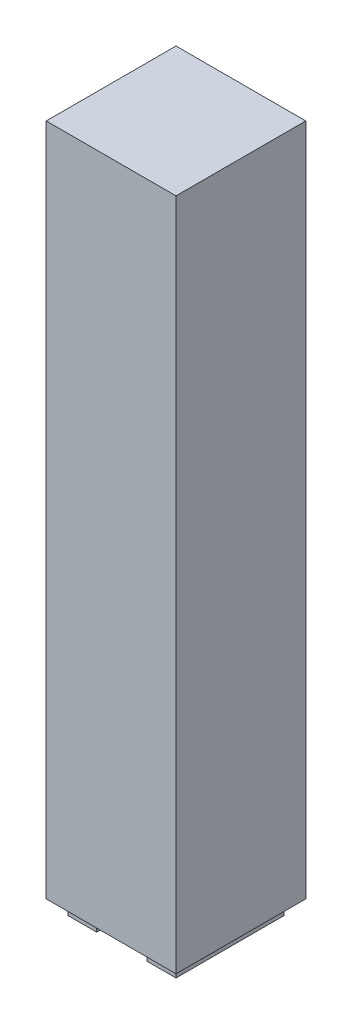
SolidWorks part; units mm, degrees
ref_plane "Front Plane" through (0, 0, 0) normal (0, 0, 1) x (1, 0, 0)
ref_plane "Top Plane" through (0, 0, 0) normal (0, 1, 0) x (1, 0, 0)
ref_plane "Right Plane" through (0, 0, 0) normal (1, 0, 0) x (0, 0, -1)
sketch "Sketch1" plane through (0, 0, 0) normal (0, 1, 0) x (1, 0, 0)
  line L1 (0, 0) -> (36, 0)
  line L2 (0, 0) -> (0, 36)
  line L3 (0, 36) -> (36, 36)
  line L4 (36, 0) -> (36, 36)
  dimension "D1" = 36
  dimension "D2" = 36
extrude "Boss-Extrude1" add sketch "Sketch1" along normal blind 186.9
sketch "Sketch2" plane through (0, 0, 0) normal (0, -1, 0) x (1, 0, 0)
  line L0 (0, 0) -> (36, 0) construction
  line L1 (3, -3) -> (7, -3)
  line L2 (3, -3) -> (3, -33)
  line L3 (3, -33) -> (7, -33)
  line L4 (7, -11) -> (7, -25)
  line L5 (36, -36) -> (0, -36) construction
  line L6 (0, -36) -> (0, 0) construction
  line L20 (36, 0) -> (36, -36) construction
  line L29 (7, -3) -> (11, -3)
  line L31 (7, -11) -> (11, -11)
  line L32 (11, -3) -> (11, -11)
  line L33 (7, -25) -> (11, -25)
  line L35 (7, -33) -> (11, -33)
  line L36 (11, -25) -> (11, -33)
  line L45 (29, -3) -> (33, -3)
  line L46 (29, -11) -> (29, -25)
  line L47 (29, -33) -> (33, -33)
  line L48 (33, -3) -> (33, -33)
  line L50 (29, -3) -> (25, -3)
  line L52 (29, -11) -> (25, -11)
  line L53 (25, -3) -> (25, -11)
  line L54 (29, -33) -> (25, -33)
  line L56 (29, -25) -> (25, -25)
  line L57 (25, -33) -> (25, -25)
  dimension "D1" = 3
  dimension "D2" = 3
  dimension "D3" = 3
  dimension "D4" = 4
  dimension "D5" = 4
  dimension "D6" = 8
  dimension "D7" = 8
  dimension "D8" = 4
  dimension "D9" = 3
  dimension "D10" = 3
  dimension "D11" = 3
  dimension "D12" = 4
  dimension "D13" = 4
  dimension "D14" = 4
extrude "Boss-Extrude2" add sketch "Sketch2" along normal blind 4
sketch "Sketch3" plane through (0, 0, 0) normal (0, -1, 0) x (1, 0, 0)
  line L0 (36, -36) -> (0, -36) construction
  line L2 (0, -36) -> (0, 0) construction
  circle A0 centre (18, -18) radius 2
  dimension "D1" = 4
  dimension "D2" = 18
  dimension "D3" = 18
extrude "Cut-Extrude1" cut sketch "Sketch3" against normal blind 5
